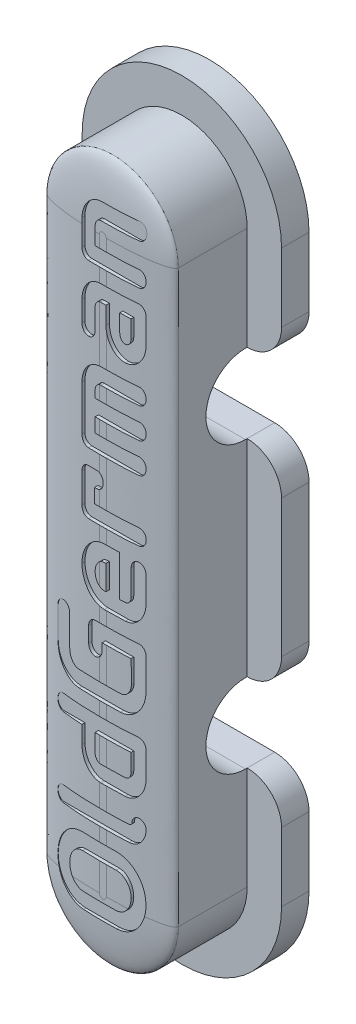
SolidWorks part; units mm, degrees
ref_plane "Front" through (0, 0, 0) normal (0, 0, 1) x (1, 0, 0)
ref_plane "Top" through (0, 0, 0) normal (0, 1, 0) x (1, 0, 0)
ref_plane "Right" through (0, 0, 0) normal (1, 0, 0) x (0, 0, -1)
sketch "草图1" plane through (0, 0, 0) normal (0, 0, 1) x (1, 0, 0)
  line L0 (0.6, -78.273) -> (0.6, -61.673) construction
  line L1 (-1.3, -78.273) -> (-1.3, -61.673)
  line L2 (2.5, -78.273) -> (2.5, -61.673)
  arc A0 (-1.3, -78.273) -> (2.5, -78.273) centre (0.6, -78.273) ccw
  arc A1 (2.5, -61.673) -> (-1.3, -61.673) centre (0.6, -61.673) ccw
  point P4 (0.6, -69.973)
  dimension "D1" = 3.8
extrude "凸台-拉伸1" add sketch "草图1" along normal blind 3.1
sketch "草图2" plane through (0, 0, 0) normal (0, 0, -1) x (-1, 0, 0)
  line L8 (2.3, -78.273) -> (2.3, -61.673)
  line L9 (-3.5, -61.673) -> (-3.5, -78.273)
  line L10 (2.3, -78.273) -> (2.3, -61.673)
  line L11 (-3.5, -61.673) -> (-3.5, -78.273)
  arc A8 (-3.5, -78.273) -> (2.3, -78.273) centre (-0.6, -78.273) ccw
  arc A9 (2.3, -61.673) -> (-3.5, -61.673) centre (-0.6, -61.673) ccw
  arc A10 (-3.5, -78.273) -> (2.3, -78.273) centre (-0.6, -78.273) ccw
  arc A11 (2.3, -61.673) -> (-3.5, -61.673) centre (-0.6, -61.673) ccw
  dimension "D1" = 1
extrude "凸台-拉伸2" add sketch "草图2" against normal blind 0.8
ref_plane "基准面1" through (0, 0, 3.1) normal (0, 0, 1) x (1, 0, 0)
fillet "圆角1" radius 0.3 4 edges at (2.5, -69.973, 3.1) (0.6, -59.773, 3.1) (0.6, -80.173, 3.1) (-1.3, -69.973, 3.1) second distance 1.8 first distance on face at (2.5, -69.973, 1.95) first distance on face at (0.6, -60.723, 1.95) first distance on face at (0.6, -79.223, 1.95) first distance on face at (-1.3, -69.973, 1.95)
sketch "草图3" plane through (0, 0, 0) normal (0, 0, -1) x (-1, 0, 0)
  line L0 (-0.6, -61.673) -> (-0.6, -78.273) construction
  circle A0 centre (-0.6, -61.673) radius 1
  circle A1 centre (-0.6, -69.973) radius 1.0967
  circle A2 centre (-0.6, -78.273) radius 1.0967
  point P9 (-0.6, -69.973)
  dimension "D1" = 2
extrude "凸台-拉伸3" add sketch "草图3" along normal blind 1.05
sketch "草图6" plane through (0, 0, 0) normal (0, 0, -1) x (-1, 0, 0)
  line L0 (-0.6, -78.273) -> (-0.6, -69.973) construction
  line L1 (-0.6, -69.973) -> (-0.6, -61.673) construction
  line L2 (-3.5, -61.673) -> (-3.5, -78.273) construction
  line L3 (2.3, -75.273) -> (-3.5, -75.273)
  line L4 (2.3, -75.273) -> (2.3, -72.973)
  line L5 (2.3, -72.973) -> (-3.5, -72.973)
  line L6 (-3.5, -75.273) -> (-3.5, -72.973)
  line L7 (2.3, -75.273) -> (-3.5, -72.973) construction
  line L8 (2.3, -72.973) -> (-3.5, -75.273) construction
  line L10 (2.3, -66.973) -> (-3.5, -66.973)
  line L11 (2.3, -66.973) -> (2.3, -64.673)
  line L12 (2.3, -64.673) -> (-3.5, -64.673)
  line L13 (-3.5, -66.973) -> (-3.5, -64.673)
  line L14 (2.3, -66.973) -> (-3.5, -64.673) construction
  line L15 (2.3, -64.673) -> (-3.5, -66.973) construction
  point P4 (-0.6, -74.123)
  point P13 (-0.6, -65.823)
  dimension "D1" = 2.3
extrude "切除-拉伸2" cut sketch "草图6" against normal blind 2
fillet "圆角4" radius 1 8 edges at (-2.3, -75.273, 0.4) (-2.3, -64.673, 0.4) (3.5, -64.673, 0.4) (3.5, -66.973, 0.4) (-2.3, -66.973, 0.4) (-2.3, -72.973, 0.4) (3.5, -72.973, 0.4) (3.5, -75.273, 0.4)
fillet "圆角2" 2 edges at (0.6, -72.973, 2) (0.6, -75.273, 2) type full round first side face at (0.6, -72.973, 0.9333) second side face at (0.6, -75.273, 0.9333) middle face at (0.6, -74.123, 2)
fillet "圆角3" 2 edges at (0.6, -64.673, 2) (0.6, -66.973, 2) type full round first side face at (0.6, -64.673, 0.9333) second side face at (0.6, -66.973, 0.9333) middle face at (0.6, -65.823, 2)
fillet "圆角5" radius 0.9 3 edges at (1.6, -61.673, 0) (1.6967, -69.973, 0) (1.6967, -78.273, 0)
sketch "草图5" plane through (0, 0, 3.1) normal (0, 0, 1) x (1, 0, 0)
  line L0 (1.801, -60.7382) -> (1.801, -79.2175) construction
  text T1 "OldGerman" font "DS ISO 1" height 2.6
extrude "切除-拉伸3" cut sketch "草图5" against normal blind 0.1
